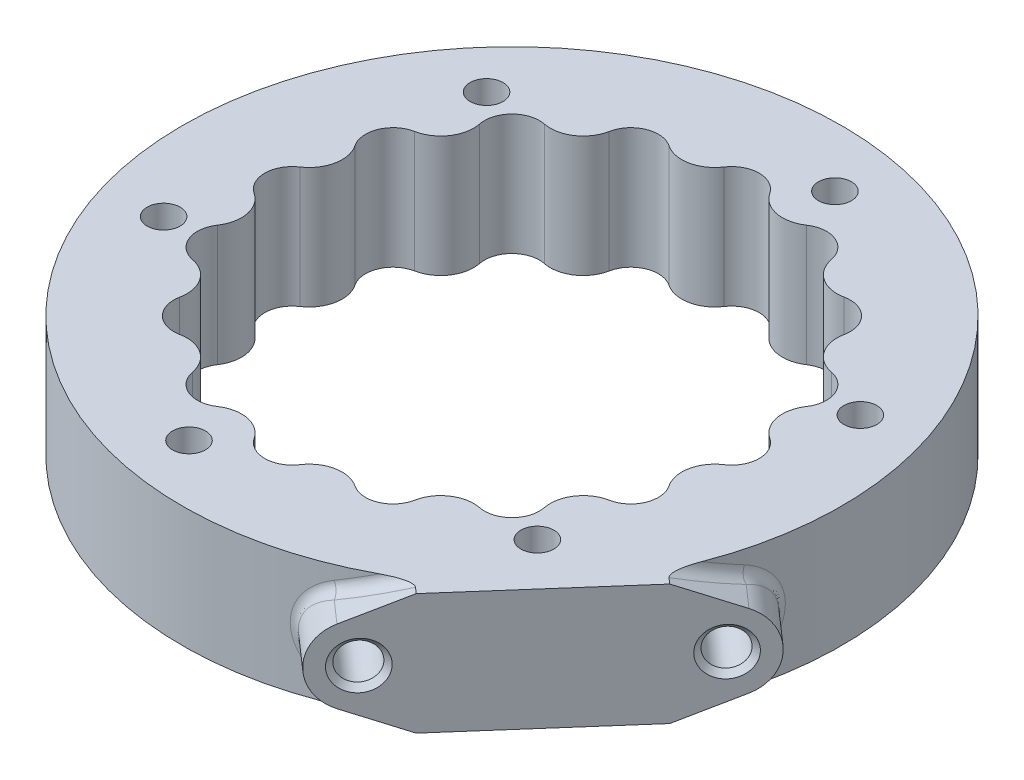
SolidWorks part; units mm, degrees
note: '?' marks a value the reader was unsure of.
ref_plane "Front Plane" through (0, 0, 0) normal (0, 0, 1) x (1, 0, 0)
ref_plane "Top Plane" through (0, 0, 0) normal (0, 1, 0) x (1, 0, 0)
ref_plane "Right Plane" through (0, 0, 0) normal (1, 0, 0) x (0, 0, -1)
sketch "Sketch1" plane through (0, 0, 0) normal (0, 1, 0) x (1, 0, 0)
  arc A0 (-31.5919, 24.5347) -> (-34.7568, 19.7981) centre (0, 0) ccw
  arc A1 (4.9902, 39.6875) -> (-4.9902, 39.6875) centre (0, 40) ccw
  arc A2 (19.7981, 34.7568) -> (10.5774, 38.5761) centre (15.3073, 36.9552) ccw
  arc A3 (-31.5919, 24.5347) -> (-34.7568, 19.7981) centre (0, 0) ccw construction
  arc A4 (31.5919, 24.5347) -> (24.5347, 31.5919) centre (28.2843, 28.2843) ccw
  arc A5 (-31.5919, 24.5347) -> (-34.7568, 19.7981) centre (0, 0) ccw construction
  arc A6 (38.5761, 10.5774) -> (34.7568, 19.7981) centre (36.9552, 15.3073) ccw
  arc A7 (-31.5919, 24.5347) -> (-34.7568, 19.7981) centre (0, 0) ccw construction
  arc A8 (39.6875, -4.9902) -> (39.6875, 4.9902) centre (40, 0) ccw
  arc A9 (-31.5919, 24.5347) -> (-34.7568, 19.7981) centre (0, 0) ccw construction
  arc A10 (34.7568, -19.7981) -> (38.5761, -10.5774) centre (36.9552, -15.3073) ccw
  arc A11 (-31.5919, 24.5347) -> (-34.7568, 19.7981) centre (0, 0) ccw construction
  arc A12 (24.5347, -31.5919) -> (31.5919, -24.5347) centre (28.2843, -28.2843) ccw
  arc A13 (-31.5919, 24.5347) -> (-34.7568, 19.7981) centre (0, 0) ccw construction
  arc A14 (10.5774, -38.5761) -> (19.7981, -34.7568) centre (15.3073, -36.9552) ccw
  arc A15 (-31.5919, 24.5347) -> (-34.7568, 19.7981) centre (0, 0) ccw construction
  arc A16 (-4.9902, -39.6875) -> (4.9902, -39.6875) centre (0, -40) ccw
  arc A17 (-31.5919, 24.5347) -> (-34.7568, 19.7981) centre (0, 0) ccw construction
  arc A18 (-19.7981, -34.7568) -> (-10.5774, -38.5761) centre (-15.3073, -36.9552) ccw
  arc A19 (-31.5919, 24.5347) -> (-34.7568, 19.7981) centre (0, 0) ccw construction
  arc A20 (-31.5919, -24.5347) -> (-24.5347, -31.5919) centre (-28.2843, -28.2843) ccw
  arc A21 (-31.5919, 24.5347) -> (-34.7568, 19.7981) centre (0, 0) ccw construction
  arc A22 (-38.5761, -10.5774) -> (-34.7568, -19.7981) centre (-36.9552, -15.3073) ccw
  arc A23 (-31.5919, 24.5347) -> (-34.7568, 19.7981) centre (0, 0) ccw construction
  arc A24 (-39.6875, 4.9902) -> (-39.6875, -4.9902) centre (-40, 0) ccw
  arc A25 (-31.5919, 24.5347) -> (-34.7568, 19.7981) centre (0, 0) ccw construction
  arc A26 (-34.7568, 19.7981) -> (-38.5761, 10.5774) centre (-36.9552, 15.3073) ccw
  arc A27 (-31.5919, 24.5347) -> (-34.7568, 19.7981) centre (0, 0) ccw construction
  arc A28 (-24.5347, 31.5919) -> (-31.5919, 24.5347) centre (-28.2843, 28.2843) ccw
  arc A29 (-31.5919, 24.5347) -> (-34.7568, 19.7981) centre (0, 0) ccw construction
  arc A30 (-10.5774, 38.5761) -> (-19.7981, 34.7568) centre (-15.3073, 36.9552) ccw
  arc A31 (-31.5919, 24.5347) -> (-34.7568, 19.7981) centre (0, 0) ccw construction
  circle A32 centre (0, 0) radius 60
  arc A33 (-19.7981, 34.7568) -> (-24.5347, 31.5919) centre (0, 0) ccw
  arc A34 (-19.7981, 34.7568) -> (-24.5347, 31.5919) centre (0, 0) ccw construction
  arc A35 (-19.7981, 34.7568) -> (-24.5347, 31.5919) centre (0, 0) ccw construction
  arc A36 (-19.7981, 34.7568) -> (-24.5347, 31.5919) centre (0, 0) ccw construction
  arc A37 (-19.7981, 34.7568) -> (-24.5347, 31.5919) centre (0, 0) ccw construction
  arc A38 (-19.7981, 34.7568) -> (-24.5347, 31.5919) centre (0, 0) ccw construction
  arc A39 (-19.7981, 34.7568) -> (-24.5347, 31.5919) centre (0, 0) ccw construction
  arc A40 (-19.7981, 34.7568) -> (-24.5347, 31.5919) centre (0, 0) ccw construction
  arc A41 (-19.7981, 34.7568) -> (-24.5347, 31.5919) centre (0, 0) ccw construction
  arc A42 (-19.7981, 34.7568) -> (-24.5347, 31.5919) centre (0, 0) ccw construction
  arc A43 (-19.7981, 34.7568) -> (-24.5347, 31.5919) centre (0, 0) ccw construction
  arc A44 (-19.7981, 34.7568) -> (-24.5347, 31.5919) centre (0, 0) ccw construction
  arc A45 (-19.7981, 34.7568) -> (-24.5347, 31.5919) centre (0, 0) ccw construction
  arc A46 (-19.7981, 34.7568) -> (-24.5347, 31.5919) centre (0, 0) ccw construction
  arc A47 (-19.7981, 34.7568) -> (-24.5347, 31.5919) centre (0, 0) ccw construction
  arc A48 (-19.7981, 34.7568) -> (-24.5347, 31.5919) centre (0, 0) ccw construction
  arc A49 (-4.9902, 39.6875) -> (-10.5774, 38.5761) centre (0, 0) ccw
  arc A50 (-4.9902, 39.6875) -> (-10.5774, 38.5761) centre (0, 0) ccw construction
  arc A51 (-4.9902, 39.6875) -> (-10.5774, 38.5761) centre (0, 0) ccw construction
  arc A52 (-4.9902, 39.6875) -> (-10.5774, 38.5761) centre (0, 0) ccw construction
  arc A53 (-4.9902, 39.6875) -> (-10.5774, 38.5761) centre (0, 0) ccw construction
  arc A54 (-4.9902, 39.6875) -> (-10.5774, 38.5761) centre (0, 0) ccw construction
  arc A55 (-4.9902, 39.6875) -> (-10.5774, 38.5761) centre (0, 0) ccw construction
  arc A56 (-4.9902, 39.6875) -> (-10.5774, 38.5761) centre (0, 0) ccw construction
  arc A57 (-4.9902, 39.6875) -> (-10.5774, 38.5761) centre (0, 0) ccw construction
  arc A58 (-4.9902, 39.6875) -> (-10.5774, 38.5761) centre (0, 0) ccw construction
  arc A59 (-4.9902, 39.6875) -> (-10.5774, 38.5761) centre (0, 0) ccw construction
  arc A60 (-4.9902, 39.6875) -> (-10.5774, 38.5761) centre (0, 0) ccw construction
  arc A61 (-4.9902, 39.6875) -> (-10.5774, 38.5761) centre (0, 0) ccw construction
  arc A62 (-4.9902, 39.6875) -> (-10.5774, 38.5761) centre (0, 0) ccw construction
  arc A63 (-4.9902, 39.6875) -> (-10.5774, 38.5761) centre (0, 0) ccw construction
  arc A64 (-4.9902, 39.6875) -> (-10.5774, 38.5761) centre (0, 0) ccw construction
  arc A65 (10.5774, 38.5761) -> (4.9902, 39.6875) centre (0, 0) ccw
  arc A66 (10.5774, 38.5761) -> (4.9902, 39.6875) centre (0, 0) ccw construction
  arc A67 (10.5774, 38.5761) -> (4.9902, 39.6875) centre (0, 0) ccw construction
  arc A68 (10.5774, 38.5761) -> (4.9902, 39.6875) centre (0, 0) ccw construction
  arc A69 (10.5774, 38.5761) -> (4.9902, 39.6875) centre (0, 0) ccw construction
  arc A70 (10.5774, 38.5761) -> (4.9902, 39.6875) centre (0, 0) ccw construction
  arc A71 (10.5774, 38.5761) -> (4.9902, 39.6875) centre (0, 0) ccw construction
  arc A72 (10.5774, 38.5761) -> (4.9902, 39.6875) centre (0, 0) ccw construction
  arc A73 (10.5774, 38.5761) -> (4.9902, 39.6875) centre (0, 0) ccw construction
  arc A74 (10.5774, 38.5761) -> (4.9902, 39.6875) centre (0, 0) ccw construction
  arc A75 (10.5774, 38.5761) -> (4.9902, 39.6875) centre (0, 0) ccw construction
  arc A76 (10.5774, 38.5761) -> (4.9902, 39.6875) centre (0, 0) ccw construction
  arc A77 (10.5774, 38.5761) -> (4.9902, 39.6875) centre (0, 0) ccw construction
  arc A78 (10.5774, 38.5761) -> (4.9902, 39.6875) centre (0, 0) ccw construction
  arc A79 (10.5774, 38.5761) -> (4.9902, 39.6875) centre (0, 0) ccw construction
  arc A80 (10.5774, 38.5761) -> (4.9902, 39.6875) centre (0, 0) ccw construction
  arc A81 (24.5347, 31.5919) -> (19.7981, 34.7568) centre (0, 0) ccw
  arc A82 (24.5347, 31.5919) -> (19.7981, 34.7568) centre (0, 0) ccw construction
  arc A83 (24.5347, 31.5919) -> (19.7981, 34.7568) centre (0, 0) ccw construction
  arc A84 (24.5347, 31.5919) -> (19.7981, 34.7568) centre (0, 0) ccw construction
  arc A85 (24.5347, 31.5919) -> (19.7981, 34.7568) centre (0, 0) ccw construction
  arc A86 (24.5347, 31.5919) -> (19.7981, 34.7568) centre (0, 0) ccw construction
  arc A87 (24.5347, 31.5919) -> (19.7981, 34.7568) centre (0, 0) ccw construction
  arc A88 (24.5347, 31.5919) -> (19.7981, 34.7568) centre (0, 0) ccw construction
  arc A89 (24.5347, 31.5919) -> (19.7981, 34.7568) centre (0, 0) ccw construction
  arc A90 (24.5347, 31.5919) -> (19.7981, 34.7568) centre (0, 0) ccw construction
  arc A91 (24.5347, 31.5919) -> (19.7981, 34.7568) centre (0, 0) ccw construction
  arc A92 (24.5347, 31.5919) -> (19.7981, 34.7568) centre (0, 0) ccw construction
  arc A93 (24.5347, 31.5919) -> (19.7981, 34.7568) centre (0, 0) ccw construction
  arc A94 (24.5347, 31.5919) -> (19.7981, 34.7568) centre (0, 0) ccw construction
  arc A95 (24.5347, 31.5919) -> (19.7981, 34.7568) centre (0, 0) ccw construction
  arc A96 (24.5347, 31.5919) -> (19.7981, 34.7568) centre (0, 0) ccw construction
  arc A97 (34.7568, 19.7981) -> (31.5919, 24.5347) centre (0, 0) ccw
  arc A98 (34.7568, 19.7981) -> (31.5919, 24.5347) centre (0, 0) ccw construction
  arc A99 (34.7568, 19.7981) -> (31.5919, 24.5347) centre (0, 0) ccw construction
  arc A100 (34.7568, 19.7981) -> (31.5919, 24.5347) centre (0, 0) ccw construction
  arc A101 (34.7568, 19.7981) -> (31.5919, 24.5347) centre (0, 0) ccw construction
  arc A102 (34.7568, 19.7981) -> (31.5919, 24.5347) centre (0, 0) ccw construction
  arc A103 (34.7568, 19.7981) -> (31.5919, 24.5347) centre (0, 0) ccw construction
  arc A104 (34.7568, 19.7981) -> (31.5919, 24.5347) centre (0, 0) ccw construction
  arc A105 (34.7568, 19.7981) -> (31.5919, 24.5347) centre (0, 0) ccw construction
  arc A106 (34.7568, 19.7981) -> (31.5919, 24.5347) centre (0, 0) ccw construction
  arc A107 (34.7568, 19.7981) -> (31.5919, 24.5347) centre (0, 0) ccw construction
  arc A108 (34.7568, 19.7981) -> (31.5919, 24.5347) centre (0, 0) ccw construction
  arc A109 (34.7568, 19.7981) -> (31.5919, 24.5347) centre (0, 0) ccw construction
  arc A110 (34.7568, 19.7981) -> (31.5919, 24.5347) centre (0, 0) ccw construction
  arc A111 (34.7568, 19.7981) -> (31.5919, 24.5347) centre (0, 0) ccw construction
  arc A112 (34.7568, 19.7981) -> (31.5919, 24.5347) centre (0, 0) ccw construction
  arc A113 (39.6875, 4.9902) -> (38.5761, 10.5774) centre (0, 0) ccw
  arc A114 (39.6875, 4.9902) -> (38.5761, 10.5774) centre (0, 0) ccw construction
  arc A115 (39.6875, 4.9902) -> (38.5761, 10.5774) centre (0, 0) ccw construction
  arc A116 (39.6875, 4.9902) -> (38.5761, 10.5774) centre (0, 0) ccw construction
  arc A117 (39.6875, 4.9902) -> (38.5761, 10.5774) centre (0, 0) ccw construction
  arc A118 (39.6875, 4.9902) -> (38.5761, 10.5774) centre (0, 0) ccw construction
  arc A119 (39.6875, 4.9902) -> (38.5761, 10.5774) centre (0, 0) ccw construction
  arc A120 (39.6875, 4.9902) -> (38.5761, 10.5774) centre (0, 0) ccw construction
  arc A121 (39.6875, 4.9902) -> (38.5761, 10.5774) centre (0, 0) ccw construction
  arc A122 (39.6875, 4.9902) -> (38.5761, 10.5774) centre (0, 0) ccw construction
  arc A123 (39.6875, 4.9902) -> (38.5761, 10.5774) centre (0, 0) ccw construction
  arc A124 (39.6875, 4.9902) -> (38.5761, 10.5774) centre (0, 0) ccw construction
  arc A125 (39.6875, 4.9902) -> (38.5761, 10.5774) centre (0, 0) ccw construction
  arc A126 (39.6875, 4.9902) -> (38.5761, 10.5774) centre (0, 0) ccw construction
  arc A127 (39.6875, 4.9902) -> (38.5761, 10.5774) centre (0, 0) ccw construction
  arc A128 (39.6875, 4.9902) -> (38.5761, 10.5774) centre (0, 0) ccw construction
  arc A129 (38.5761, -10.5774) -> (39.6875, -4.9902) centre (0, 0) ccw
  arc A130 (38.5761, -10.5774) -> (39.6875, -4.9902) centre (0, 0) ccw construction
  arc A131 (38.5761, -10.5774) -> (39.6875, -4.9902) centre (0, 0) ccw construction
  arc A132 (38.5761, -10.5774) -> (39.6875, -4.9902) centre (0, 0) ccw construction
  arc A133 (38.5761, -10.5774) -> (39.6875, -4.9902) centre (0, 0) ccw construction
  arc A134 (38.5761, -10.5774) -> (39.6875, -4.9902) centre (0, 0) ccw construction
  arc A135 (38.5761, -10.5774) -> (39.6875, -4.9902) centre (0, 0) ccw construction
  arc A136 (38.5761, -10.5774) -> (39.6875, -4.9902) centre (0, 0) ccw construction
  arc A137 (38.5761, -10.5774) -> (39.6875, -4.9902) centre (0, 0) ccw construction
  arc A138 (38.5761, -10.5774) -> (39.6875, -4.9902) centre (0, 0) ccw construction
  arc A139 (38.5761, -10.5774) -> (39.6875, -4.9902) centre (0, 0) ccw construction
  arc A140 (38.5761, -10.5774) -> (39.6875, -4.9902) centre (0, 0) ccw construction
  arc A141 (38.5761, -10.5774) -> (39.6875, -4.9902) centre (0, 0) ccw construction
  arc A142 (38.5761, -10.5774) -> (39.6875, -4.9902) centre (0, 0) ccw construction
  arc A143 (38.5761, -10.5774) -> (39.6875, -4.9902) centre (0, 0) ccw construction
  arc A144 (38.5761, -10.5774) -> (39.6875, -4.9902) centre (0, 0) ccw construction
  arc A145 (31.5919, -24.5347) -> (34.7568, -19.7981) centre (0, 0) ccw
  arc A146 (31.5919, -24.5347) -> (34.7568, -19.7981) centre (0, 0) ccw construction
  arc A147 (31.5919, -24.5347) -> (34.7568, -19.7981) centre (0, 0) ccw construction
  arc A148 (31.5919, -24.5347) -> (34.7568, -19.7981) centre (0, 0) ccw construction
  arc A149 (31.5919, -24.5347) -> (34.7568, -19.7981) centre (0, 0) ccw construction
  arc A150 (31.5919, -24.5347) -> (34.7568, -19.7981) centre (0, 0) ccw construction
  arc A151 (31.5919, -24.5347) -> (34.7568, -19.7981) centre (0, 0) ccw construction
  arc A152 (31.5919, -24.5347) -> (34.7568, -19.7981) centre (0, 0) ccw construction
  arc A153 (31.5919, -24.5347) -> (34.7568, -19.7981) centre (0, 0) ccw construction
  arc A154 (31.5919, -24.5347) -> (34.7568, -19.7981) centre (0, 0) ccw construction
  arc A155 (31.5919, -24.5347) -> (34.7568, -19.7981) centre (0, 0) ccw construction
  arc A156 (31.5919, -24.5347) -> (34.7568, -19.7981) centre (0, 0) ccw construction
  arc A157 (31.5919, -24.5347) -> (34.7568, -19.7981) centre (0, 0) ccw construction
  arc A158 (31.5919, -24.5347) -> (34.7568, -19.7981) centre (0, 0) ccw construction
  arc A159 (31.5919, -24.5347) -> (34.7568, -19.7981) centre (0, 0) ccw construction
  arc A160 (31.5919, -24.5347) -> (34.7568, -19.7981) centre (0, 0) ccw construction
  arc A161 (19.7981, -34.7568) -> (24.5347, -31.5919) centre (0, 0) ccw
  arc A162 (19.7981, -34.7568) -> (24.5347, -31.5919) centre (0, 0) ccw construction
  arc A163 (19.7981, -34.7568) -> (24.5347, -31.5919) centre (0, 0) ccw construction
  arc A164 (19.7981, -34.7568) -> (24.5347, -31.5919) centre (0, 0) ccw construction
  arc A165 (19.7981, -34.7568) -> (24.5347, -31.5919) centre (0, 0) ccw construction
  arc A166 (19.7981, -34.7568) -> (24.5347, -31.5919) centre (0, 0) ccw construction
  arc A167 (19.7981, -34.7568) -> (24.5347, -31.5919) centre (0, 0) ccw construction
  arc A168 (19.7981, -34.7568) -> (24.5347, -31.5919) centre (0, 0) ccw construction
  arc A169 (19.7981, -34.7568) -> (24.5347, -31.5919) centre (0, 0) ccw construction
  arc A170 (19.7981, -34.7568) -> (24.5347, -31.5919) centre (0, 0) ccw construction
  arc A171 (19.7981, -34.7568) -> (24.5347, -31.5919) centre (0, 0) ccw construction
  arc A172 (19.7981, -34.7568) -> (24.5347, -31.5919) centre (0, 0) ccw construction
  arc A173 (19.7981, -34.7568) -> (24.5347, -31.5919) centre (0, 0) ccw construction
  arc A174 (19.7981, -34.7568) -> (24.5347, -31.5919) centre (0, 0) ccw construction
  arc A175 (19.7981, -34.7568) -> (24.5347, -31.5919) centre (0, 0) ccw construction
  arc A176 (19.7981, -34.7568) -> (24.5347, -31.5919) centre (0, 0) ccw construction
  arc A177 (4.9902, -39.6875) -> (10.5774, -38.5761) centre (0, 0) ccw
  arc A178 (4.9902, -39.6875) -> (10.5774, -38.5761) centre (0, 0) ccw construction
  arc A179 (4.9902, -39.6875) -> (10.5774, -38.5761) centre (0, 0) ccw construction
  arc A180 (4.9902, -39.6875) -> (10.5774, -38.5761) centre (0, 0) ccw construction
  arc A181 (4.9902, -39.6875) -> (10.5774, -38.5761) centre (0, 0) ccw construction
  arc A182 (4.9902, -39.6875) -> (10.5774, -38.5761) centre (0, 0) ccw construction
  arc A183 (4.9902, -39.6875) -> (10.5774, -38.5761) centre (0, 0) ccw construction
  arc A184 (4.9902, -39.6875) -> (10.5774, -38.5761) centre (0, 0) ccw construction
  arc A185 (4.9902, -39.6875) -> (10.5774, -38.5761) centre (0, 0) ccw construction
  arc A186 (4.9902, -39.6875) -> (10.5774, -38.5761) centre (0, 0) ccw construction
  arc A187 (4.9902, -39.6875) -> (10.5774, -38.5761) centre (0, 0) ccw construction
  arc A188 (4.9902, -39.6875) -> (10.5774, -38.5761) centre (0, 0) ccw construction
  arc A189 (4.9902, -39.6875) -> (10.5774, -38.5761) centre (0, 0) ccw construction
  arc A190 (4.9902, -39.6875) -> (10.5774, -38.5761) centre (0, 0) ccw construction
  arc A191 (4.9902, -39.6875) -> (10.5774, -38.5761) centre (0, 0) ccw construction
  arc A192 (4.9902, -39.6875) -> (10.5774, -38.5761) centre (0, 0) ccw construction
  arc A193 (-10.5774, -38.5761) -> (-4.9902, -39.6875) centre (0, 0) ccw
  arc A194 (-10.5774, -38.5761) -> (-4.9902, -39.6875) centre (0, 0) ccw construction
  arc A195 (-10.5774, -38.5761) -> (-4.9902, -39.6875) centre (0, 0) ccw construction
  arc A196 (-10.5774, -38.5761) -> (-4.9902, -39.6875) centre (0, 0) ccw construction
  arc A197 (-10.5774, -38.5761) -> (-4.9902, -39.6875) centre (0, 0) ccw construction
  arc A198 (-10.5774, -38.5761) -> (-4.9902, -39.6875) centre (0, 0) ccw construction
  arc A199 (-10.5774, -38.5761) -> (-4.9902, -39.6875) centre (0, 0) ccw construction
  arc A200 (-10.5774, -38.5761) -> (-4.9902, -39.6875) centre (0, 0) ccw construction
  arc A201 (-10.5774, -38.5761) -> (-4.9902, -39.6875) centre (0, 0) ccw construction
  arc A202 (-10.5774, -38.5761) -> (-4.9902, -39.6875) centre (0, 0) ccw construction
  arc A203 (-10.5774, -38.5761) -> (-4.9902, -39.6875) centre (0, 0) ccw construction
  arc A204 (-10.5774, -38.5761) -> (-4.9902, -39.6875) centre (0, 0) ccw construction
  arc A205 (-10.5774, -38.5761) -> (-4.9902, -39.6875) centre (0, 0) ccw construction
  arc A206 (-10.5774, -38.5761) -> (-4.9902, -39.6875) centre (0, 0) ccw construction
  arc A207 (-10.5774, -38.5761) -> (-4.9902, -39.6875) centre (0, 0) ccw construction
  arc A208 (-10.5774, -38.5761) -> (-4.9902, -39.6875) centre (0, 0) ccw construction
  arc A209 (-24.5347, -31.5919) -> (-19.7981, -34.7568) centre (0, 0) ccw
  arc A210 (-24.5347, -31.5919) -> (-19.7981, -34.7568) centre (0, 0) ccw construction
  arc A211 (-24.5347, -31.5919) -> (-19.7981, -34.7568) centre (0, 0) ccw construction
  arc A212 (-24.5347, -31.5919) -> (-19.7981, -34.7568) centre (0, 0) ccw construction
  arc A213 (-24.5347, -31.5919) -> (-19.7981, -34.7568) centre (0, 0) ccw construction
  arc A214 (-24.5347, -31.5919) -> (-19.7981, -34.7568) centre (0, 0) ccw construction
  arc A215 (-24.5347, -31.5919) -> (-19.7981, -34.7568) centre (0, 0) ccw construction
  arc A216 (-24.5347, -31.5919) -> (-19.7981, -34.7568) centre (0, 0) ccw construction
  arc A217 (-24.5347, -31.5919) -> (-19.7981, -34.7568) centre (0, 0) ccw construction
  arc A218 (-24.5347, -31.5919) -> (-19.7981, -34.7568) centre (0, 0) ccw construction
  arc A219 (-24.5347, -31.5919) -> (-19.7981, -34.7568) centre (0, 0) ccw construction
  arc A220 (-24.5347, -31.5919) -> (-19.7981, -34.7568) centre (0, 0) ccw construction
  arc A221 (-24.5347, -31.5919) -> (-19.7981, -34.7568) centre (0, 0) ccw construction
  arc A222 (-24.5347, -31.5919) -> (-19.7981, -34.7568) centre (0, 0) ccw construction
  arc A223 (-24.5347, -31.5919) -> (-19.7981, -34.7568) centre (0, 0) ccw construction
  arc A224 (-24.5347, -31.5919) -> (-19.7981, -34.7568) centre (0, 0) ccw construction
  arc A225 (-34.7568, -19.7981) -> (-31.5919, -24.5347) centre (0, 0) ccw
  arc A226 (-34.7568, -19.7981) -> (-31.5919, -24.5347) centre (0, 0) ccw construction
  arc A227 (-34.7568, -19.7981) -> (-31.5919, -24.5347) centre (0, 0) ccw construction
  arc A228 (-34.7568, -19.7981) -> (-31.5919, -24.5347) centre (0, 0) ccw construction
  arc A229 (-34.7568, -19.7981) -> (-31.5919, -24.5347) centre (0, 0) ccw construction
  arc A230 (-34.7568, -19.7981) -> (-31.5919, -24.5347) centre (0, 0) ccw construction
  arc A231 (-34.7568, -19.7981) -> (-31.5919, -24.5347) centre (0, 0) ccw construction
  arc A232 (-34.7568, -19.7981) -> (-31.5919, -24.5347) centre (0, 0) ccw construction
  arc A233 (-34.7568, -19.7981) -> (-31.5919, -24.5347) centre (0, 0) ccw construction
  arc A234 (-34.7568, -19.7981) -> (-31.5919, -24.5347) centre (0, 0) ccw construction
  arc A235 (-34.7568, -19.7981) -> (-31.5919, -24.5347) centre (0, 0) ccw construction
  arc A236 (-34.7568, -19.7981) -> (-31.5919, -24.5347) centre (0, 0) ccw construction
  arc A237 (-34.7568, -19.7981) -> (-31.5919, -24.5347) centre (0, 0) ccw construction
  arc A238 (-34.7568, -19.7981) -> (-31.5919, -24.5347) centre (0, 0) ccw construction
  arc A239 (-34.7568, -19.7981) -> (-31.5919, -24.5347) centre (0, 0) ccw construction
  arc A240 (-34.7568, -19.7981) -> (-31.5919, -24.5347) centre (0, 0) ccw construction
  arc A241 (-39.6875, -4.9902) -> (-38.5761, -10.5774) centre (0, 0) ccw
  arc A242 (-39.6875, -4.9902) -> (-38.5761, -10.5774) centre (0, 0) ccw construction
  arc A243 (-39.6875, -4.9902) -> (-38.5761, -10.5774) centre (0, 0) ccw construction
  arc A244 (-39.6875, -4.9902) -> (-38.5761, -10.5774) centre (0, 0) ccw construction
  arc A245 (-39.6875, -4.9902) -> (-38.5761, -10.5774) centre (0, 0) ccw construction
  arc A246 (-39.6875, -4.9902) -> (-38.5761, -10.5774) centre (0, 0) ccw construction
  arc A247 (-39.6875, -4.9902) -> (-38.5761, -10.5774) centre (0, 0) ccw construction
  arc A248 (-39.6875, -4.9902) -> (-38.5761, -10.5774) centre (0, 0) ccw construction
  arc A249 (-39.6875, -4.9902) -> (-38.5761, -10.5774) centre (0, 0) ccw construction
  arc A250 (-39.6875, -4.9902) -> (-38.5761, -10.5774) centre (0, 0) ccw construction
  arc A251 (-39.6875, -4.9902) -> (-38.5761, -10.5774) centre (0, 0) ccw construction
  arc A252 (-39.6875, -4.9902) -> (-38.5761, -10.5774) centre (0, 0) ccw construction
  arc A253 (-39.6875, -4.9902) -> (-38.5761, -10.5774) centre (0, 0) ccw construction
  arc A254 (-39.6875, -4.9902) -> (-38.5761, -10.5774) centre (0, 0) ccw construction
  arc A255 (-39.6875, -4.9902) -> (-38.5761, -10.5774) centre (0, 0) ccw construction
  arc A256 (-39.6875, -4.9902) -> (-38.5761, -10.5774) centre (0, 0) ccw construction
  arc A257 (-38.5761, 10.5774) -> (-39.6875, 4.9902) centre (0, 0) ccw
  arc A258 (-38.5761, 10.5774) -> (-39.6875, 4.9902) centre (0, 0) ccw construction
  arc A259 (-38.5761, 10.5774) -> (-39.6875, 4.9902) centre (0, 0) ccw construction
  arc A260 (-38.5761, 10.5774) -> (-39.6875, 4.9902) centre (0, 0) ccw construction
  arc A261 (-38.5761, 10.5774) -> (-39.6875, 4.9902) centre (0, 0) ccw construction
  arc A262 (-38.5761, 10.5774) -> (-39.6875, 4.9902) centre (0, 0) ccw construction
  arc A263 (-38.5761, 10.5774) -> (-39.6875, 4.9902) centre (0, 0) ccw construction
  arc A264 (-38.5761, 10.5774) -> (-39.6875, 4.9902) centre (0, 0) ccw construction
  arc A265 (-38.5761, 10.5774) -> (-39.6875, 4.9902) centre (0, 0) ccw construction
  arc A266 (-38.5761, 10.5774) -> (-39.6875, 4.9902) centre (0, 0) ccw construction
  arc A267 (-38.5761, 10.5774) -> (-39.6875, 4.9902) centre (0, 0) ccw construction
  arc A268 (-38.5761, 10.5774) -> (-39.6875, 4.9902) centre (0, 0) ccw construction
  arc A269 (-38.5761, 10.5774) -> (-39.6875, 4.9902) centre (0, 0) ccw construction
  arc A270 (-38.5761, 10.5774) -> (-39.6875, 4.9902) centre (0, 0) ccw construction
  arc A271 (-38.5761, 10.5774) -> (-39.6875, 4.9902) centre (0, 0) ccw construction
  arc A272 (-38.5761, 10.5774) -> (-39.6875, 4.9902) centre (0, 0) ccw construction
  point P52 (0, 0)
  dimension "D1" = 80
  dimension "D2" = 10
  dimension "D4" = 120
  dimension "D3" = 16
extrude "Boss-Extrude1" add sketch "Sketch1" along normal blind 22
fillet "Fillet1" radius 5 32 edges at (-31.5919, 11, -24.5347) (-34.7568, 11, -19.7981) (10.5774, 11, 38.5761) (4.9902, 11, 39.6875) (-4.9902, 11, 39.6875) (-10.5774, 11, 38.5761) (-19.7981, 11, 34.7568) (-24.5347, 11, 31.5919) (-31.5919, 11, 24.5347) (-34.7568, 11, 19.7981) (-38.5761, 11, 10.5774) (-39.6875, 11, 4.9902) (-39.6875, 11, -4.9902) (-38.5761, 11, -10.5774) (19.7981, 11, 34.7568) (24.5347, 11, 31.5919) (31.5919, 11, 24.5347) (34.7568, 11, 19.7981) (38.5761, 11, 10.5774) (39.6875, 11, 4.9902) (39.6875, 11, -4.9902) (38.5761, 11, -10.5774) (34.7568, 11, -19.7981) (31.5919, 11, -24.5347) (24.5347, 11, -31.5919) (19.7981, 11, -34.7568) (10.5774, 11, -38.5761) (4.9902, 11, -39.6875) (-4.9902, 11, -39.6875) (-10.5774, 11, -38.5761) (-19.7981, 11, -34.7568) (-24.5347, 11, -31.5919)
fillet "Fillet2" radius 6 16 edges at (-7.8059, 11, 39.2431) (7.8059, 11, 39.2431) (22.2294, 11, 33.2687) (33.2687, 11, 22.2294) (-22.2294, 11, 33.2687) (-33.2687, 11, 22.2294) (-39.2431, 11, 7.8059) (-39.2431, 11, -7.8059) (39.2431, 11, 7.8059) (39.2431, 11, -7.8059) (33.2687, 11, -22.2294) (22.2294, 11, -33.2687) (7.8059, 11, -39.2431) (-7.8059, 11, -39.2431) (-22.2294, 11, -33.2687) (-33.2687, 11, -22.2294)
sketch "Sketch3" plane through (0, 22, 0) normal (0, 1, 0) x (1, 0, 0)
  line L0 (7.9956, 40.1966) -> (11.7054, 58.8471) construction
  circle A0 centre (0, 0) radius 50 construction
  circle A4 centre (9.7545, 49.0393) radius 3
  arc A5 (4.1664, 42.7642) -> (12.5159, 41.1034) centre (9.1661, 46.0813) ccw construction
  circle A6 centre (0, 0) radius 60 construction
  circle A7 centre (47.3465, 16.072) radius 3
  circle A8 centre (37.592, -32.9673) radius 3
  circle A9 centre (-9.7545, -49.0393) radius 3
  circle A10 centre (-47.3465, -16.072) radius 3
  circle A11 centre (-37.592, 32.9673) radius 3
  point P13 (9.1661, 46.0813)
  point P31 (0, 0)
  dimension "D1" = 100
  dimension "D2" = 6
  dimension "D3" = 6
extrude "Cut-Extrude1" cut sketch "Sketch3" against normal through all
ref_axis "Axis1" through (37.592, 0, 32.9673) along (0, 1, 0)?
ref_axis "Axis2" through (-9.7545, 0, 49.0393) along (0, 1, 0)?
ref_plane "Plane1" through (13.9187, 0, 41.0033) normal (-0.3214, 0, -0.9469) x (-0.9469, 0, 0.3214)
ref_plane "Plane2" through (19.2864, 0, 56.8158) normal (0.3214, 0, 0.9469) x (0.9469, 0, -0.3214)
ref_plane "Plane3" through (19.6078, 0, 57.7627) normal (0.3214, 0, 0.9469) x (0.9469, 0, -0.3214)
ref_plane "Plane4" through (45.1104, 0, 39.5607) normal (0.7518, 0, 0.6593) x (0, -1, 0)
ref_plane "Plane5" through (45.8622, 0, 40.2201) normal (0.7518, 0, 0.6593) x (0, -1, 0)
sketch "Sketch6" plane through (48.3229, 0, 37.4142) normal (-0.7518, 0, -0.6593) x (-0.6593, 0, 0.7518)
  line L0 (-56.2679, 0) -> (63.7321, 0) construction
  line L1 (-22.8416, 17.6775) -> (-2.6943, 26.1971)
  line L2 (10.1584, 26.1971) -> (30.3057, 17.6775)
  line L3 (-22.8416, 4.3225) -> (-2.6943, -4.1971)
  line L4 (10.1584, -4.1971) -> (30.3057, 4.3225)
  arc A0 (-2.6943, -4.1971) -> (10.1584, -4.1971) centre (3.7321, 11) ccw
  arc A1 (30.3057, 4.3225) -> (30.3057, 17.6775) centre (27.4821, 11) ccw
  arc A2 (-22.8416, 17.6775) -> (-22.8416, 4.3225) centre (-20.0179, 11) ccw
  arc A3 (10.1584, 26.1971) -> (-2.6943, 26.1971) centre (3.7321, 11) ccw
  dimension "D1" = 33
  dimension "D2" = 23.75
  dimension "D3" = 23.75
  dimension "D4" = 11
extrude "Boss-Extrude3" add sketch "Sketch6" against normal up to surface (1.3451 mm away)
sketch "Sketch7" plane through (45.8622, 0, 40.2201) normal (0.7518, 0, 0.6593) x (0.6593, 0, -0.7518)
  circle A0 centre (23.75, 11) radius 3.3
  circle A1 centre (-23.75, 11) radius 3.3
  dimension "D1" = 6.6
extrude "Cut-Extrude3" cut sketch "Sketch7" against normal blind 10.5
chamfer "Chamfer2" distance 1 angle 45 2 edges at (63.6975, 11, 19.8828) (32.3786, 11, 55.5952)
fillet "Fillet3" radius 2 6 edges at (56.3102, 19.8007, 20.7161) (56.3102, 2.1993, 20.7161) (27.8889, 2.1993, 53.1245) (27.8889, 19.8007, 53.1245) (59.03, 9.4978, 10.745) (18.3581, 12.5022, 57.1225)
sketch "Sketch8" plane through (45.8622, 0, 40.2201) normal (0.7518, 0, 0.6593) x (0.6593, 0, -0.7518)
  line L1 (-16.3518, 22) -> (16.3518, 22)
  line L2 (-16.3518, 22) -> (-16.3518, 27.5)
  line L3 (-16.3518, 27.5) -> (16.3518, 27.5)
  line L4 (16.3518, 22) -> (16.3518, 27.5)
  line L6 (-16.3518, -5.5) -> (16.3518, -5.5)
  line L7 (-16.3518, -5.5) -> (-16.3518, 0)
  line L8 (-16.3518, 0) -> (16.3518, 0)
  line L9 (16.3518, -5.5) -> (16.3518, 0)
  line L10 (26.5737, 4.3225) -> (6.4263, -4.1971) construction
  line L11 (60, 22) -> (-60, 22) construction
  arc A0 (6.4263, 26.1971) -> (-6.4263, 26.1971) centre (0, 11) ccw construction
  arc A1 (-6.4263, -4.1971) -> (6.4263, -4.1971) centre (0, 11) ccw construction
extrude "Cut-Extrude4" cut sketch "Sketch8" against normal through all
equation "\"R_ROLL\"= 5mm"
equation "\"D_SUN\"= 80mm"
equation "\"NUM_ROLL\"= 16"
equation "\"RHO\"= 1mm"
equation "\"D_SHAFT\"= 15mm"
equation "\"D_OUTPUT\"= 40mm"
equation "\"NUM_OUT\"= 6"
equation "\"R_OUT_ROLL\"= 5mm"
equation "\"D1@Sketch1\"=\"D_SUN\""
equation "\"D2@Sketch1\"=\"R_ROLL\"*2"
equation "\"D3@Sketch1\"=\"NUM_ROLL\""
equation "\"D4@Sketch1\"=\"D_SUN\"+40"
